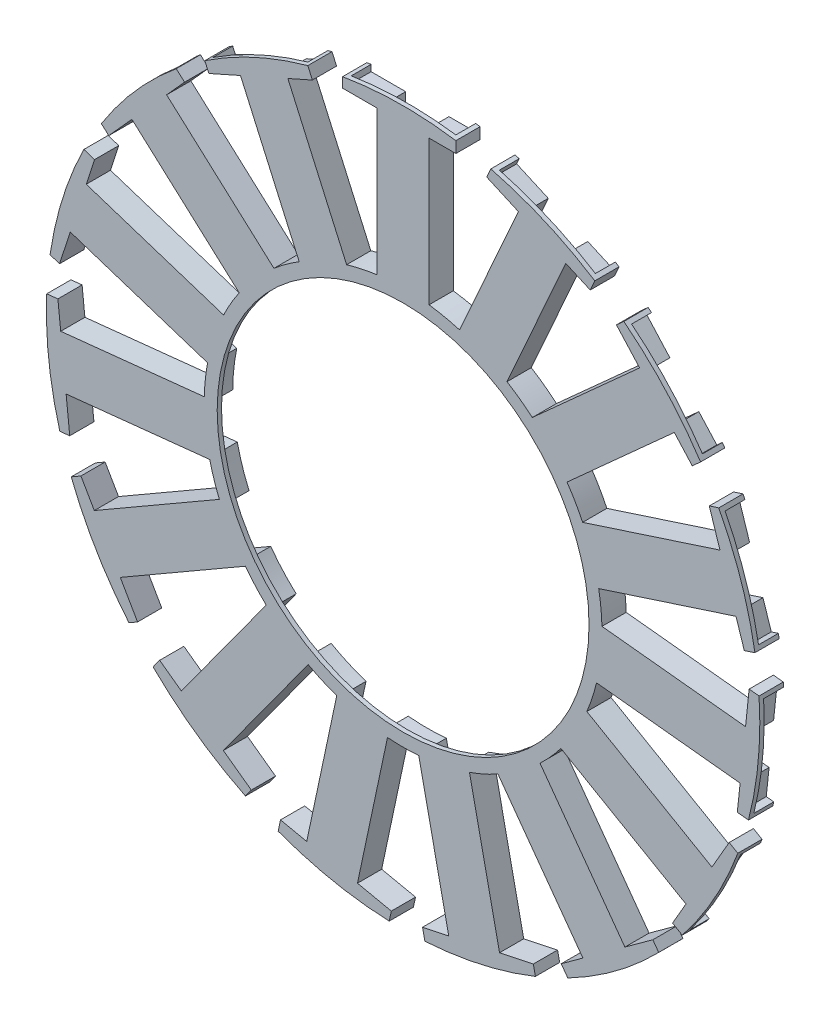
SolidWorks part; units mm, degrees
material "ABS"
ref_plane "正面" through (0, 0, 0) normal (0, 0, 1) x (1, 0, 0)
ref_plane "平面" through (0, 0, 0) normal (0, 1, 0) x (1, 0, 0)
ref_plane "右側面" through (0, 0, 0) normal (1, 0, 0) x (0, 0, -1)
sketch "ｽｹｯﾁ1" plane through (0, 0, 0) normal (0, 0, 1) x (1, 0, 0)
  line L0 (0, 0) -> (0, 40)
  line L1 (0, 0) -> (-2.5, 0)
  line L2 (-2.5, 0) -> (-2.5, 40)
  line L3 (0, 0) -> (2.5, 0)
  line L4 (2.5, 0) -> (2.5, 40)
  line L6 (-2.5, 40) -> (-6.5, 40)
  line L7 (2.5, 40) -> (5.6, 40)
  line L8 (5.6, 40) -> (5.6, 43.6422)
  line L9 (-6.5, 40) -> (-6.5, 43.5172)
  arc A1 (5.6, 43.6422) -> (-6.5, 43.5172) centre (0, 0) ccw
  circle A2 centre (0, 0) radius 22.5
  dimension "D2" = 88
  dimension "D3" = 45
  dimension "D4" = 2.5
  dimension "D5" = 2.5
  dimension "D7" = 6.5
  dimension "D8" = 5.6
extrude "ﾎﾞｽ - 押し出し2" add sketch "ｽｹｯﾁ1" along normal blind 2.3 contours L2 A2 L4 L3 L1 | L1 L2 L6 L9 A1 L8 L7 L4 L3 region at (0, -0.8527, 0)
pattern_circular "円形ﾊﾟﾀｰﾝ2" count 15 over 360 about axis through (0, 0, 2.3) along (0, 0, 1) of "ﾎﾞｽ - 押し出し2"
sketch "ｽｹｯﾁ3" plane through (0, 0, 2.3) normal (0, 0, 1) x (1, 0, 0)
  circle A0 centre (0, 0) radius 3.25
  dimension "D1" = 6.5
extrude "ｶｯﾄ - 押し出し2" cut sketch "ｽｹｯﾁ3" against normal blind 3.2
sketch "ｽｹｯﾁ5" plane through (0, 0, 2.3) normal (0, 0, 1) x (1, 0, 0)
  line L0 (-15, 0) -> (15, 0)
  line L1 (0, 0) -> (0, -15.75)
  line L2 (-10.4775, -15.75) -> (10.4775, -15.75)
  circle A0 centre (-15, 0) radius 1.6
  circle A1 centre (15, 0) radius 1.6
  circle A2 centre (10.4775, -15.75) radius 1.6
  circle A3 centre (-10.4775, -15.75) radius 1.6
  point P5 (0, 0)
  point P11 (0, -15.75)
  point P17 (0, 17)
  dimension "D1" = 3.2
  dimension "D4" = 3.2
  dimension "D5" = 3.2
  dimension "D2" = 15.75
  dimension "D3" = 10.4775
extrude "ｶｯﾄ - 押し出し3" cut sketch "ｽｹｯﾁ5" against normal blind 10 contours A0 | A1 | A3 | A2
sketch "ｽｹｯﾁ6" plane through (0, 0, 2.3) normal (0, 0, 1) x (1, 0, 0)
  line L0 (0, 0) -> (-16.6, 0)
  line L1 (-16.6, 0) -> (-16.6, 8)
  line L2 (0, 0) -> (0, 11.5739)
  line L3 (-16.6, 0) -> (-18.1, 0)
  line L4 (-18.1, 0) -> (-18.1, -8)
  circle A0 centre (-15, 0) radius 1.6 construction
  circle A1 centre (-16.6, 8) radius 1.6
  circle A5 centre (-18.1, -8) radius 1.6
  circle A6 centre (18.1, -8) radius 1.6
  circle A7 centre (16.6, 8) radius 1.6
  dimension "D2" = 3.2
  dimension "D5" = 3.2
  dimension "D1" = 8
  dimension "D3" = 1.5
  dimension "D4" = 8
  dimension "D6" = 16.6
extrude "ｶｯﾄ - 押し出し4" cut sketch "ｽｹｯﾁ6" against normal blind 10 contours A1 | A5 | A6 | A7
shell "ｼｪﾙ2" thickness 0.5 removed face at (-16.5, -8, 0) outward yes
sketch "ｽｹｯﾁ8" plane through (0, 0, 2.3) normal (0, 0, -1) x (-1, 0, 0)
  circle A0 centre (0, 0) radius 21.5
  dimension "D1" = 43
extrude "ｶｯﾄ - 押し出し6" cut sketch "ｽｹｯﾁ8" against normal blind 10 and the other way blind 10
sketch "ｽｹｯﾁ9" plane through (0, 0, 2.3) normal (0, 0, -1) x (-1, 0, 0)
  circle A0 centre (0, 0) radius 41.25
  circle A1 centre (0, 0) radius 60.0324
  dimension "D1" = 82.5
extrude "ｶｯﾄ - 押し出し7" cut sketch "ｽｹｯﾁ9" against normal blind 10 and the other way blind 10
